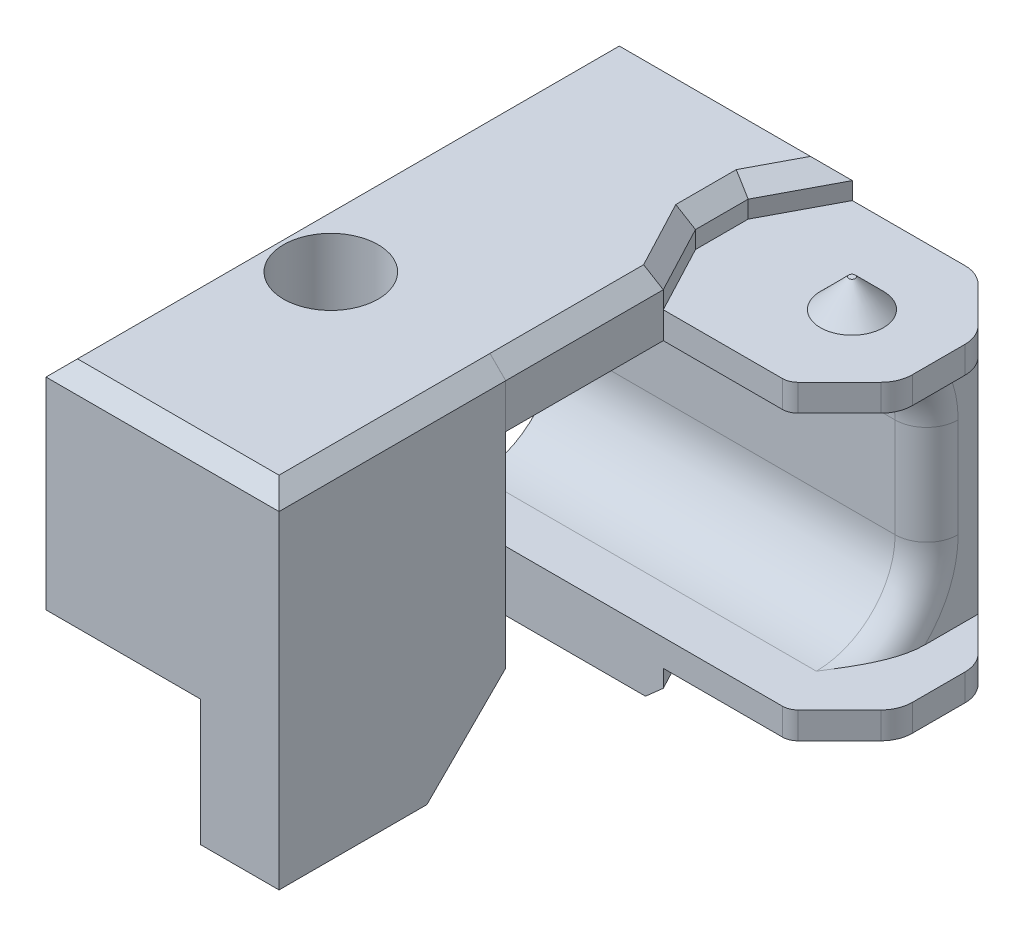
SolidWorks part; units mm, degrees
ref_plane "Plano frontal" through (0, 0, 0) normal (0, 0, 1) x (1, 0, 0)
ref_plane "Plano superior" through (0, 0, 0) normal (0, 1, 0) x (1, 0, 0)
ref_plane "Plano direito" through (0, 0, 0) normal (1, 0, 0) x (0, 0, -1)
sketch "Esboço1" plane through (0, 0, 0) normal (0, 1, 0) x (1, 0, 0)
  line L8 (4.91, 19.3882) -> (0, 19.3882)
  line L9 (0, 19.3882) -> (0, 0)
  line L10 (0, 0) -> (9.7908, 0)
  line L11 (9.7908, 0) -> (9.7908, 14.3877)
  arc A2 (9.7908, 14.3877) -> (4.91, 19.3882) centre (4.7908, 14.3896) ccw
sketch "Esboço2" plane through (0, 0, 0) normal (0, 1, 0) x (1, 0, 0)
  line L2 (14.7908, 0) -> (14.7908, 14.3867)
  line L3 (4.9594, 24.3882) -> (0, 24.3882)
  line L4 (4.91, 19.3882) -> (0, 19.3882)
  line L5 (0, 19.3882) -> (0, 0)
  line L6 (0, 0) -> (9.7908, 0)
  line L7 (9.7908, 0) -> (9.7908, 14.3877)
  line L8 (4.91, 19.3882) -> (0, 19.3882)
  line L9 (0, 24.3882) -> (0, 0)
  line L10 (0, 0) -> (14.7908, 0)
  line L11 (9.7908, 0) -> (9.7908, 14.3877)
  line L12 (-5, 24.3882) -> (-5, -5) construction
  line L13 (0, 19.3882) -> (0, 0) construction
  line L14 (4.9594, 24.3882) -> (-5, 24.3882) construction
  line L15 (-5, -5) -> (14.7908, -5) construction
  line L16 (0, 0) -> (9.7908, 0) construction
  line L17 (14.7908, -5) -> (14.7908, 14.3867) construction
  arc A0 (14.7908, 14.3867) -> (4.9594, 24.3882) centre (4.7908, 14.3896) ccw
  arc A1 (9.7908, 14.3877) -> (4.91, 19.3882) centre (4.7908, 14.3896) ccw
  arc A2 (9.7908, 14.3877) -> (4.91, 19.3882) centre (4.7908, 14.3896) ccw
  dimension "D1" = 0
  dimension "D2" = 5
extrude "Ressalto-extrusão1" add sketch "Esboço2" along normal blind 3.8 contours L11 A2 L8 L9 L10 | A2 L11 L10 L2 A0 L3 L9 L8 region at (12.2908, 0, -0.2852) region at (4.7856, 0, -9.445)
sketch "Esboço3" plane through (0, 0, 0) normal (0, 1, 0) x (1, 0, 0)
  line L0 (4.91, 19.3882) -> (0, 19.3882) construction
  line L1 (9.7908, 0) -> (9.7908, 14.3877) construction
  line L2 (4.91, 19.3882) -> (0, 19.3882)
  line L3 (9.7908, 0) -> (9.7908, 14.3877)
  line L4 (14.7908, 0) -> (14.7908, 14.3867)
  line L5 (4.9594, 24.3882) -> (0, 24.3882)
  line L6 (0, 24.3882) -> (0, 0)
  line L7 (0, 0) -> (14.7908, 0)
  line L8 (14.7908, 0) -> (14.7908, 14.3867)
  line L9 (4.9594, 24.3882) -> (0, 24.3882)
  line L10 (0, 24.3882) -> (0, 0)
  line L11 (0, 0) -> (14.7908, 0)
  line L12 (14.7908, 14.3867) -> (9.7908, 14.3877)
  arc A0 (9.7908, 14.3877) -> (4.91, 19.3882) centre (4.7908, 14.3896) ccw construction
  arc A1 (14.7908, 14.3867) -> (4.9594, 24.3882) centre (4.7908, 14.3896) ccw
  arc A2 (14.7908, 14.3867) -> (4.9594, 24.3882) centre (4.7908, 14.3896) ccw
  arc A3 (9.7908, 14.3877) -> (4.91, 19.3882) centre (4.7908, 14.3896) ccw
  dimension "D1" = 0
sketch "Esboço4" plane through (0, 3.8, 0) normal (0, 1, 0) x (1, 0, 0)
  line L0 (9.7908, 0) -> (9.7908, 14.3877) construction
  line L3 (4.91, 19.3882) -> (0, 19.3882) construction
  circle A0 centre (4.2608, 13.8182) radius 1.75
  dimension "D3" = 3.5
  dimension "D1" = 5.53
  dimension "D2" = 5.57
sketch "Esboço7" plane through (0, 3.8, 0) normal (0, 1, 0) x (1, 0, 0)
  line L33 (0, 36.3882) -> (0, 24.3882)
  line L34 (0, 24.3882) -> (22.352, 24.3882)
  line L35 (23.0591, 24.6811) -> (25.6804, 27.3024)
  line L36 (26.2662, 28.7166) -> (26.2662, 32.0597)
  line L37 (25.6804, 33.474) -> (23.352, 35.8024)
  line L38 (21.9378, 36.3882) -> (19.75, 36.3882)
  line L39 (19.75, 36.3882) -> (0, 36.3882)
  line L40 (14.7908, 14.3896) -> (14.7908, 24.3882)
  line L42 (0, 24.3882) -> (14.7908, 24.3882)
  line L43 (0, 24.3882) -> (0, 14.3896)
  line L44 (0, 14.3896) -> (14.7908, 14.3896)
  line L45 (14.7908, 24.3882) -> (14.7908, 14.3896)
  arc A18 (22.352, 24.3882) -> (23.0591, 24.6811) centre (22.352, 25.3882) ccw
  arc A19 (25.6804, 27.3024) -> (26.2662, 28.7166) centre (24.2662, 28.7166) ccw
  arc A20 (26.2662, 32.0597) -> (25.6804, 33.474) centre (24.2662, 32.0597) ccw
  arc A21 (23.352, 35.8024) -> (21.9378, 36.3882) centre (21.9378, 34.3882) ccw
  arc A22 (14.7908, 14.3867) -> (4.9594, 24.3882) centre (4.7908, 14.3896) ccw construction
  arc M2 (14.7908, 14.3867) -> (4.9594, 24.3882) centre (4.7908, 14.3896) ccw
  line M4 (4.9594, 24.3882) -> (0, 24.3882)
extrude "Corte-extrusão1" cut sketch "Esboço4" against normal blind 10
extrude "Ressalto-extrusão2" add sketch "Esboço3" against normal blind 18 contours L8 L12 L3 L11 region at (12.2908, 0, -7.1936)
extrude "Ressalto-extrusão3" add sketch "Esboço7" against normal up to surface (3.8 mm away) contours L37 A21 L38 L39 L33 L34 A18 L35 A19 L36 A20 M4 | L40 L34 M2 region at (12.638, 3.8, -30.3869) region at (12.5589, 3.8, -22.1545) up to face at (4.2608, 0, -12.0682)
sketch "Esboço8" plane through (0, 3.8, 0) normal (0, 1, 0) x (1, 0, 0)
  line L0 (14.7908, 24.3882) -> (12.5051, 28.7166)
  line L1 (12.5051, 28.7166) -> (12.5051, 32.0597)
  line L2 (12.5051, 32.0597) -> (14.7908, 36.3882)
  line L10 (0, 0) -> (14.7908, 0)
  line L11 (14.7908, 0) -> (14.7908, 14.3867)
  line L12 (14.7908, 14.3867) -> (14.7908, 14.3896)
  line L13 (14.7908, 14.3896) -> (14.7908, 24.3882)
  line L14 (14.7908, 24.3882) -> (22.352, 24.3882)
  line L15 (23.0591, 24.6811) -> (25.6804, 27.3024)
  line L16 (26.2662, 28.7166) -> (26.2662, 32.0597)
  line L17 (25.6804, 33.474) -> (23.352, 35.8024)
  line L18 (21.9378, 36.3882) -> (0, 36.3882)
  line L19 (0, 36.3882) -> (0, 0)
  line L22 (14.7908, 14.3867) -> (14.7908, 14.3896)
  line L24 (14.7908, 24.3882) -> (22.352, 24.3882)
  line L25 (23.0591, 24.6811) -> (25.6804, 27.3024)
  line L26 (26.2662, 28.7166) -> (26.2662, 32.0597)
  line L27 (25.6804, 33.474) -> (23.352, 35.8024)
  line L28 (21.9378, 36.3882) -> (14.7908, 36.3882)
  arc A4 (22.352, 24.3882) -> (23.0591, 24.6811) centre (22.352, 25.3882) ccw
  arc A5 (25.6804, 27.3024) -> (26.2662, 28.7166) centre (24.2662, 28.7166) ccw
  arc A6 (26.2662, 32.0597) -> (25.6804, 33.474) centre (24.2662, 32.0597) ccw
  arc A7 (23.352, 35.8024) -> (21.9378, 36.3882) centre (21.9378, 34.3882) ccw
  arc A8 (22.352, 24.3882) -> (23.0591, 24.6811) centre (22.352, 25.3882) ccw
  arc A9 (25.6804, 27.3024) -> (26.2662, 28.7166) centre (24.2662, 28.7166) ccw
  arc A10 (26.2662, 32.0597) -> (25.6804, 33.474) centre (24.2662, 32.0597) ccw
  arc A11 (23.352, 35.8024) -> (21.9378, 36.3882) centre (21.9378, 34.3882) ccw
  line M20 (14.7908, 24.3882) -> (22.352, 24.3882)
  arc M21 (22.352, 24.3882) -> (23.0591, 24.6811) centre (22.352, 25.3882) ccw
  line M22 (23.0591, 24.6811) -> (25.6804, 27.3024)
  arc M23 (25.6804, 27.3024) -> (26.2662, 28.7166) centre (24.2662, 28.7166) ccw
  line M24 (26.2662, 28.7166) -> (26.2662, 32.0597)
  arc M25 (26.2662, 32.0597) -> (25.6804, 33.474) centre (24.2662, 32.0597) ccw
  line M26 (25.6804, 33.474) -> (23.352, 35.8024)
  arc M27 (23.352, 35.8024) -> (21.9378, 36.3882) centre (21.9378, 34.3882) ccw
  line M28 (21.9378, 36.3882) -> (0, 36.3882)
  dimension "D1" = 0
extrude "Corte-extrusão2" cut sketch "Esboço8" against normal blind 2.1 contours L2 L1 L0 M20 M21 M22 M23 M24 M25 M26 M27 M28 region at (19.3087, 3.8, -30.3855)
ref_plane "Plano1" through (0, -16.31, 0) normal (0, -1, 0) x (-1, 0, 0)
sketch "Esboço9" plane through (0, -16.31, 0) normal (0, -1, 0) x (-1, 0, 0)
  line L0 (-14.7908, 24.3882) -> (0, 24.3882)
  line L11 (-14.7908, 24.3882) -> (-14.7908, 14.3896)
  line L12 (-14.7908, 14.3896) -> (-14.7908, 14.3867)
  line L13 (-14.7908, 14.3867) -> (-9.7908, 14.3877)
  line L14 (-9.7908, 14.3877) -> (-9.7908, 0)
  line L15 (-9.7908, 0) -> (0, 0)
  line L16 (0, 0) -> (0, 36.3882)
  line L17 (0, 36.3882) -> (-21.9378, 36.3882)
  line L18 (-23.352, 35.8024) -> (-25.6804, 33.474)
  line L19 (-26.2662, 32.0597) -> (-26.2662, 28.7166)
  line L20 (-25.6804, 27.3024) -> (-23.0591, 24.6811)
  line L21 (-22.352, 24.3882) -> (-14.7908, 24.3882)
  line L23 (-14.7908, 14.3896) -> (-14.7908, 14.3867)
  line L27 (0, 24.3882) -> (0, 36.3882)
  line L28 (0, 36.3882) -> (-21.9378, 36.3882)
  line L29 (-23.352, 35.8024) -> (-25.6804, 33.474)
  line L30 (-26.2662, 32.0597) -> (-26.2662, 28.7166)
  line L31 (-25.6804, 27.3024) -> (-23.0591, 24.6811)
  line L32 (-22.352, 24.3882) -> (-14.7908, 24.3882)
  arc A4 (-21.9378, 36.3882) -> (-23.352, 35.8024) centre (-21.9378, 34.3882) ccw
  arc A5 (-25.6804, 33.474) -> (-26.2662, 32.0597) centre (-24.2662, 32.0597) ccw
  arc A6 (-26.2662, 28.7166) -> (-25.6804, 27.3024) centre (-24.2662, 28.7166) ccw
  arc A7 (-23.0591, 24.6811) -> (-22.352, 24.3882) centre (-22.352, 25.3882) ccw
  arc A8 (-21.9378, 36.3882) -> (-23.352, 35.8024) centre (-21.9378, 34.3882) ccw
  arc A9 (-25.6804, 33.474) -> (-26.2662, 32.0597) centre (-24.2662, 32.0597) ccw
  arc A10 (-26.2662, 28.7166) -> (-25.6804, 27.3024) centre (-24.2662, 28.7166) ccw
  arc A11 (-23.0591, 24.6811) -> (-22.352, 24.3882) centre (-22.352, 25.3882) ccw
  dimension "D1" = 0
extrude "Ressalto-extrusão4" add sketch "Esboço9" along normal blind 1.7 separate body contours L31 A11 L32 L0 L27 L28 A8 L29 A9 L30 A10 region at (12.638, -16.31, -30.3869)
sketch "Esboço11" plane through (0, -18.01, 0) normal (0, -1, 0) x (1, 0, 0)
  line L0 (14.7908, -24.3882) -> (0, -24.3882)
  line L9 (12.5051, -32.0597) -> (12.5051, -28.7166)
  line L10 (14.7908, -36.3882) -> (12.5051, -32.0597)
  line L11 (0, -36.3882) -> (14.7908, -36.3882)
  line L12 (0, 0) -> (0, -36.3882)
  line L13 (14.7908, 0) -> (0, 0)
  line L14 (14.7908, -14.3867) -> (14.7908, 0)
  line L15 (14.7908, -14.3896) -> (14.7908, -14.3867)
  line L16 (14.7908, -24.3882) -> (14.7908, -14.3896)
  line L17 (12.5051, -28.7166) -> (14.7908, -24.3882)
  line L18 (12.5051, -32.0597) -> (12.5051, -28.7166)
  line L19 (14.7908, -36.3882) -> (12.5051, -32.0597)
  line L20 (0, -36.3882) -> (14.7908, -36.3882)
  line L21 (0, -24.3882) -> (0, -36.3882)
  line L24 (14.7908, -14.3896) -> (14.7908, -14.3867)
  line L26 (12.5051, -28.7166) -> (14.7908, -24.3882)
  line M12 (22.352, -24.3882) -> (0, -24.3882)
  line M13 (0, -24.3882) -> (0, -36.3882)
  line M14 (0, -36.3882) -> (21.9378, -36.3882)
  dimension "D1" = 0
extrude "Ressalto-extrusão5" add sketch "Esboço11" along normal blind 2.1 contours L18 L26 L19 M12 M13 M14 region at (6.6864, -18.01, -30.3882)
sketch "Esboço12" plane through (0, 0, -36.3882) normal (0, 0, -1) x (-1, 0, 0)
  line L0 (-12.5051, 3.8) -> (-12.5051, -20.11)
  line L1 (-12.5051, 3.8) -> (0, 3.8)
  line L3 (-12.5051, -20.11) -> (0, -20.11)
  line L4 (0, 3.8) -> (0, -20.11)
extrude "Ressalto-extrusão6" add sketch "Esboço12" against normal blind 4
sketch "Esboço13" plane through (0, 1.7, 0) normal (0, 1, 0) x (1, 0, 0)
  line L0 (26.2662, 30.3882) -> (20.7662, 30.3882) construction
  line L1 (26.2662, 28.7166) -> (26.2662, 32.0597) construction
  circle A0 centre (20.7662, 30.3882) radius 2
  dimension "D2" = 4
  dimension "D1" = 5.5
extrude "Ressalto-extrusão7" add sketch "Esboço13" along normal blind 1.8 draft 45
ref_plane "Plano2" through (0, -8.155, 0) normal (0, 1, 0) x (1, 0, 0)
mirror "Espelhar1" about plane through (0, -8.155, 0) normal (0, 1, 0) of "Ressalto-extrusão7"
fillet "Filete2" radius 5 2 edges at (6.2525, -16.31, -32.3882) (6.2525, 0, -32.3882)
chamfer "Chanfro1" distance 1 angle 45 2 edges at (7.3954, -20.11, -36.3882) (7.3954, 3.8, -36.3882)
chamfer "Chanfro2" distance 5 angle 45 1 edges at (12.2908, -18, -14.3872)
chamfer "Chanfro3" distance 1 angle 45 6 edges at (13.3839, 3.8, -33.724) (12.5051, 3.8, -30.3882) (13.648, 3.8, -26.5524) (14.7908, 3.8, -19.3889) (14.7908, 3.8, -14.3882) (14.7908, 3.8, -7.1934)
chamfer "Chanfro4" distance 1 angle 45 2 edges at (6.8954, 3.8, 0) (0, 3.8, -17.6941)
chamfer "Chanfro5" distance 1 angle 45 3 edges at (13.3839, -20.11, -33.724) (12.5051, -20.11, -30.3882) (13.648, -20.11, -26.5524)
sketch "Esboço15" plane through (0, 0, 0) normal (0, -1, 0) x (1, 0, 0)
  line L0 (9.7908, 0) -> (9.7908, -9.3877) construction
  line L1 (9.7908, -14.3877) -> (9.7908, -9.3877) construction
  line L2 (0, -27.3882) -> (0, 0) construction
  line L3 (0, 0) -> (9.7908, 0) construction
  line L4 (9.7908, 0) -> (9.7908, -9.3877)
  line L5 (9.7908, -14.3877) -> (9.7908, -9.3877)
  line L6 (0, -20.5683) -> (0, 0)
  line L7 (0, 0) -> (9.7908, 0)
  line L8 (9.7908, -14.3877) -> (0, -20.5683)
  circle A0 centre (4.2608, -13.8182) radius 1.75 construction
  circle A1 centre (4.2608, -13.8182) radius 1.75
extrude "Ressalto-extrusão8" add sketch "Esboço15" along normal blind 10
sketch "Esboço14" plane through (0, 3.8, 0) normal (0, 1, 0) x (1, 0, 0)
  circle A0 centre (4.2608, 13.8182) radius 3
  dimension "D1" = 6
extrude "Corte-extrusão3" cut sketch "Esboço14" against normal blind 12.5
sketch "Esboço16" plane through (12.5051, 0, 0) normal (1, 0, 0) x (0, 0, -1)
  line L4 (36.3882, 0) -> (27.3882, 0)
  line L5 (32.3882, -5) -> (32.3882, -11.31)
  line L6 (27.3882, -16.31) -> (36.3882, -16.31)
  line L7 (36.3882, -16.31) -> (36.3882, 0)
  line L8 (36.3882, 0) -> (27.3882, 0)
  line L9 (32.3882, -5) -> (32.3882, -11.31)
  line L10 (27.3882, -16.31) -> (36.3882, -16.31)
  line L11 (36.3882, -16.31) -> (36.3882, 0)
  arc A2 (32.3882, -5) -> (27.3882, 0) centre (27.3882, -5) ccw
  arc A3 (27.3882, -16.31) -> (32.3882, -11.31) centre (27.3882, -11.31) ccw
  arc A4 (32.3882, -5) -> (27.3882, 0) centre (27.3882, -5) ccw
  arc A5 (27.3882, -16.31) -> (32.3882, -11.31) centre (27.3882, -11.31) ccw
  dimension "D1" = 0
extrude "Ressalto-extrusão9" add sketch "Esboço16" along normal blind 11
fillet "Filete3" radius 2 1 edges at (0, -5, -20.5683)
sketch "Esboço19" plane through (0, -16.31, 0) normal (0, -1, 0) x (1, 0, 0)
  line L3 (23.5051, -35.6493) -> (23.352, -35.8024)
  line L4 (21.9378, -36.3882) -> (23.5051, -36.3882)
  line L5 (23.5051, -36.3882) -> (23.5051, -35.6493)
  line L6 (23.5051, -35.6493) -> (23.352, -35.8024)
  line L7 (21.9378, -36.3882) -> (23.5051, -36.3882)
  line L8 (23.5051, -36.3882) -> (23.5051, -35.6493)
  arc A1 (21.9378, -36.3882) -> (23.352, -35.8024) centre (21.9378, -34.3882) ccw
  arc A2 (21.9378, -36.3882) -> (23.352, -35.8024) centre (21.9378, -34.3882) ccw
  dimension "D1" = 0
extrude "Corte-extrusão5" cut sketch "Esboço19" against normal blind 21
fillet "Filete4" radius 2 3 edges at (23.5051, -1.4645, -30.9237) (23.5051, -14.8455, -30.9237) (23.5051, -8.155, -32.3882)
